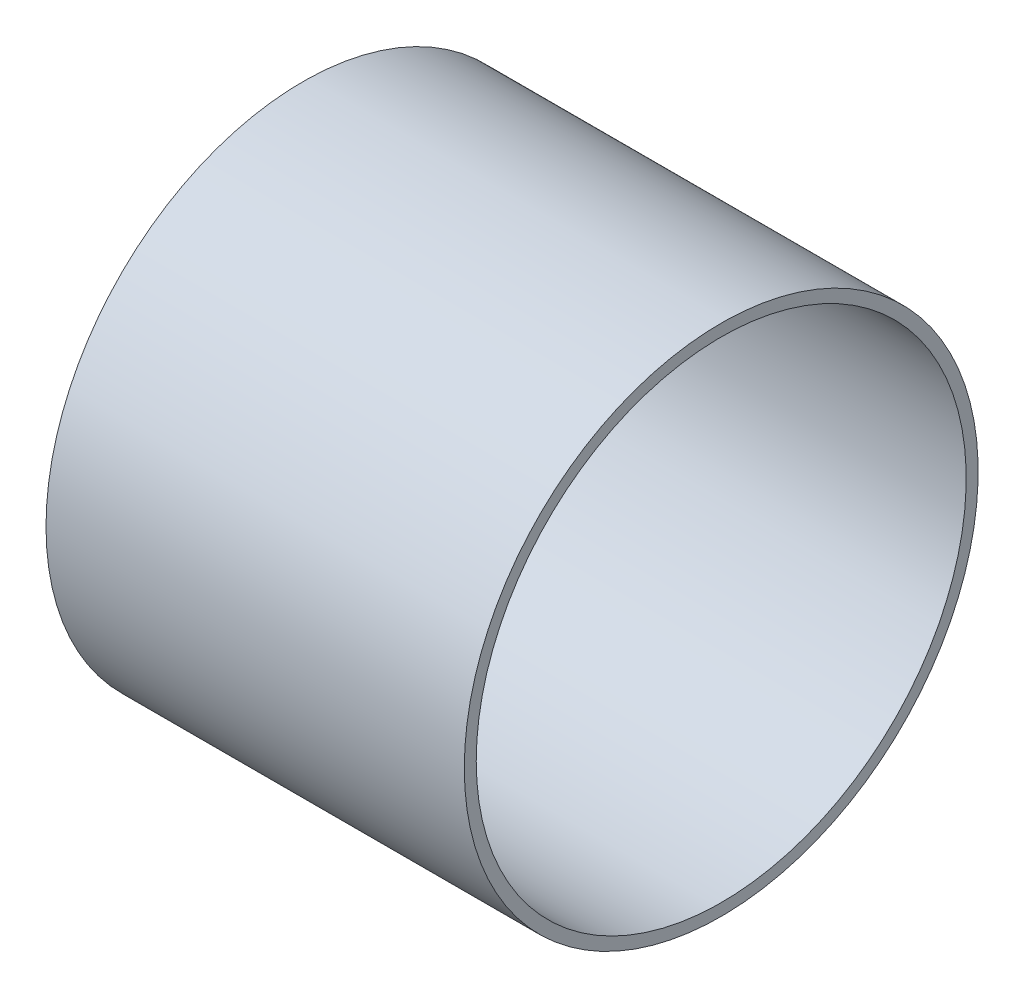
SolidWorks part; units mm, degrees
ref_plane "Plan de face" through (0, 0, 0) normal (0, 0, 1) x (1, 0, 0)
ref_plane "Plan de dessus" through (0, 0, 0) normal (0, 1, 0) x (1, 0, 0)
ref_plane "Plan de droite" through (0, 0, 0) normal (1, 0, 0) x (0, 0, -1)
sketch "Esquisse1" plane through (0, 0, 0) normal (0, 0, 1) x (1, 0, 0)
  line L0 (-29.9251, 0) -> (34.3758, 0) construction
  line L1 (-17.5, 20.5) -> (17.5, 20.5)
  line L2 (17.5, 20.5) -> (17.5, 21.5)
  line L3 (17.5, 21.5) -> (-17.5, 21.5)
  line L4 (-17.5, 21.5) -> (-17.5, 20.5)
  line L5 (0, 20.5) -> (0, 0) construction
  dimension "D1" = 43
  dimension "D2" = 41
  dimension "D3" = 35
revolve "Révolution1" add sketch "Esquisse1" angle 360 about L0
